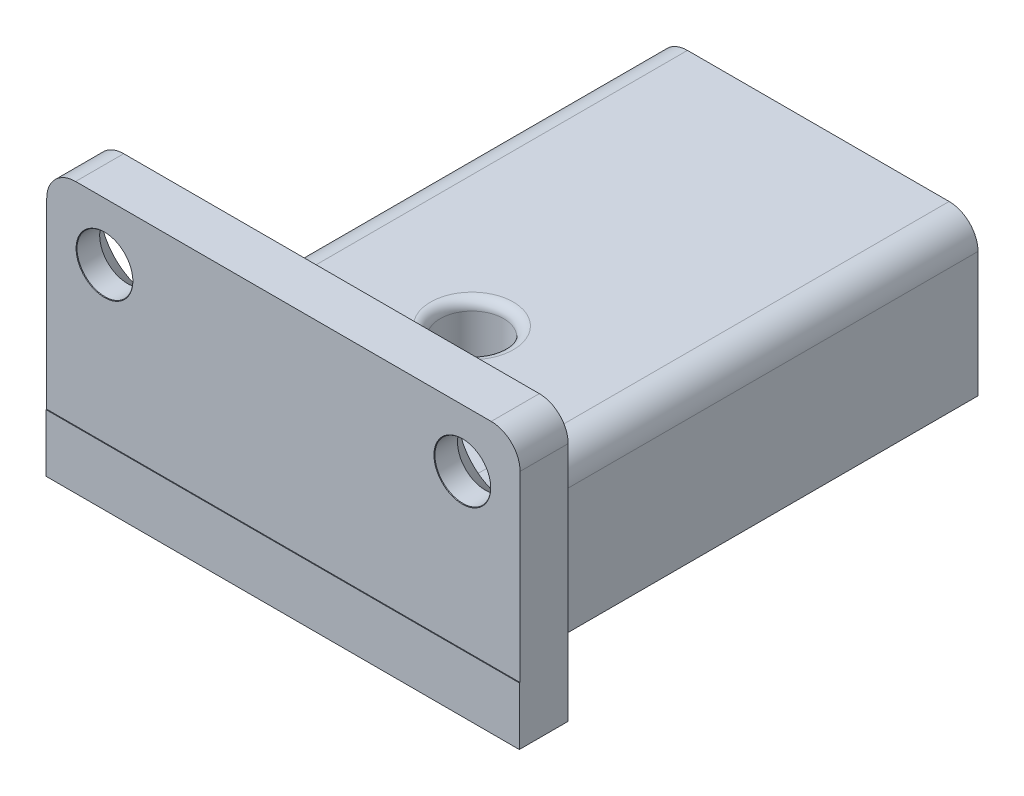
SolidWorks part; units mm, degrees
ref_plane "Plan de face" through (0, 0, 0) normal (0, 0, 1) x (1, 0, 0)
ref_plane "Plan de dessus" through (0, 0, 0) normal (0, 1, 0) x (1, 0, 0)
ref_plane "Plan de droite" through (0, 0, 0) normal (1, 0, 0) x (0, 0, -1)
sketch "Esquisse1" plane through (0, 0, 0) normal (0, 1, 0) x (1, 0, 0)
  line L0 (-6.3, 4.9618) -> (6.3, 4.9618)
  line L1 (-6.3, 4.9618) -> (-6.3, -7.8382)
  line L2 (6.3, 4.9618) -> (6.3, -7.8382)
  line L3 (-6.3, -7.8382) -> (6.3, -7.8382)
  line L4 (0, -7.8382) -> (0, 0) construction
  circle A0 centre (0, 1.9618) radius 1.65
  dimension "D4" = 3.3
  dimension "D1" = 12.8
  dimension "D2" = 12.6
  dimension "D3" = 9.8
extrude "Boss.-Extru.1" add sketch "Esquisse1" along normal blind 5
sketch "Esquisse2" plane through (0, 5, 0) normal (0, 1, 0) x (1, 0, 0)
  line L0 (-12.3, -7.8382) -> (12.3, -7.8382)
  line L1 (-12.3, -7.8382) -> (-12.3, -5.3382)
  line L2 (12.3, -7.8382) -> (12.3, -5.3382)
  line L3 (-12.3, -5.3382) -> (12.3, -5.3382)
  line L4 (-6.3, -7.8382) -> (6.3, -7.8382) construction
  line L6 (0, -7.8382) -> (0, 0.3118) construction
  line L7 (-6.3, 4.9618) -> (-6.3, -7.8382) construction
  line L8 (0, 1.9618) -> (0, 0.3118) construction
  circle A0 centre (0, 1.9618) radius 1.65 construction
  point P13 (0, 1.9618)
  dimension "D1" = 6
  dimension "D2" = 2.5
extrude "Boss.-Extru.3" add sketch "Esquisse2" along normal blind 6 and the other way through all
sketch "Esquisse4" plane through (0, 0, 5.3382) normal (0, 0, -1) x (-1, 0, 0)
  line L0 (9.3, 0) -> (9.3, 8) construction
  line L1 (6.3, 0) -> (12.3, 0) construction
  line L2 (9.3, 8) -> (-9.3, 8) construction
  line L3 (-9.3, 8) -> (-9.3, 0) construction
  line L4 (-12.3, 0) -> (-6.3, 0) construction
  line L5 (0, 5) -> (0, 11) construction
  line L6 (-6.3, 5) -> (6.3, 5) construction
  line L7 (-12.3, 11) -> (12.3, 11) construction
  point P15 (0, 8)
  point P16 (0, 8)
hole_wizard "Fraisage pour vis à tête fraisée M2.51" positions "Esquisse3D1" profile "Esquisse5" countersink size "M2.5" standard "Ansi Metric" end condition through all
sketch3d "Esquisse3D1"
  point P0 (-9.3, 8, 5.3382)
  point P3 (9.3, 8, 5.3382)
sketch "Esquisse5" plane through (-9.3, 8, 5.3382) normal (1, 0, 0) x (0, 1, 0)
  line L0 (0, 0) -> (0, 2.5)
  line L1 (0, 2.5) -> (1.475, 2.5)
  line L2 (1.45, 2.475) -> (1.45, 1.3)
  line L3 (1.45, 1.3) -> (2.75, 0)
  line L5 (2.75, 0) -> (0, 0)
  line L6 (-1.45, 1.3) -> (-2.75, 0) construction
  line L7 (1.475, 2.5) -> (1.45, 2.475)
  line L8 (-1.475, 2.5) -> (-1.45, 2.475) construction
  line L11 (0, -6.35) -> (0, 107.95) construction
  dimension "Diamètre du perçage jusqu'au prochain" = 2.9
  dimension "Profondeur du perçage jusqu'au prochain" = 2.5
  dimension "Diamètre du fraisage entrant" = 5.5
  dimension "Angle du fraisage entrant" = 90
  dimension "Diamètre du fraisage débouchant" = 2.95
  dimension "Angle du fraisage débouchant" = 90
fillet "Congé1" [suppressed] radius 1
fillet "Congé2" [suppressed] radius 1
fillet "Congé3" radius 0.5 2 edges at (0, 0, -0.3118) (0, 5, -0.3118)
sketch "Esquisse6" plane through (0, 0, -4.9618) normal (0, 0, -1) x (-1, 0, 0)
  line L0 (6.3, 5) -> (-6.3, 5)
  line L1 (6.3, 5) -> (6.3, 2)
  line L2 (-6.3, 5) -> (-6.3, 2)
  line L3 (6.3, 2) -> (-6.3, 2)
  dimension "D1" = 3
extrude "Boss.-Extru.4" add sketch "Esquisse6" along normal blind 10
sketch "Esquisse7" plane through (0, 0, -14.9618) normal (0, 0, -1) x (-1, 0, 0)
  line L0 (-6.3, 5) -> (6.3, 5)
  line L1 (-6.3, 5) -> (-6.3, 0)
  line L2 (6.3, 5) -> (6.3, 0)
  line L3 (-6.3, 0) -> (6.3, 0)
  dimension "D1" = 5
extrude "Boss.-Extru.5" add sketch "Esquisse7" along normal blind 5
sketch "Esquisse9" plane through (0, 0, 0) normal (0, -1, 0) x (1, 0, 0)
  line L0 (12.3, 5.3382) -> (-12.3, 5.3382)
  line L1 (12.3, 5.3382) -> (12.3, 7.8769)
  line L2 (-12.3, 5.3382) -> (-12.3, 7.8769)
  line L3 (12.3, 7.8769) -> (-12.3, 7.8769)
extrude "Boss.-Extru.6" add sketch "Esquisse9" along normal blind 3
sketch "Esquisse11" plane through (0, 0, 5.3382) normal (0, 0, -1) x (-1, 0, 0)
  line L0 (-6.3, 5) -> (-6.3, -3)
  line L1 (-6.3, 5) -> (-8.3, 5)
  line L2 (-6.3, -3) -> (-8.3, -3)
  line L3 (-8.3, 5) -> (-8.3, -3)
  line L4 (12.3, -3) -> (-12.3, -3) construction
  line L6 (6.3, 5) -> (8.3, 5)
  line L7 (6.3, 5) -> (6.3, -3)
  line L8 (8.3, 5) -> (8.3, -3)
  line L9 (6.3, -3) -> (8.3, -3)
  dimension "D1" = 2
extrude "Boss.-Extru.7" add sketch "Esquisse11" along normal up to surface (25.3 mm away) up to face at (0, 2.5, -19.9618)
fillet "Congé4" radius 1 3 edges at (0, 0, -14.9618) (0, 2, -14.9618) (0, 2, -4.9618)
fillet "Congé5" radius 1 2 edges at (-6.3, -3, -7.3118) (6.3, -3, -7.3118)
fillet "Congé6" radius 1.5 2 edges at (-8.3, 5, -7.3118) (8.3, 5, -7.3118)
fillet "Congé7" radius 1.5 2 edges at (12.3, 11, 6.5882) (-12.3, 11, 6.5882)
